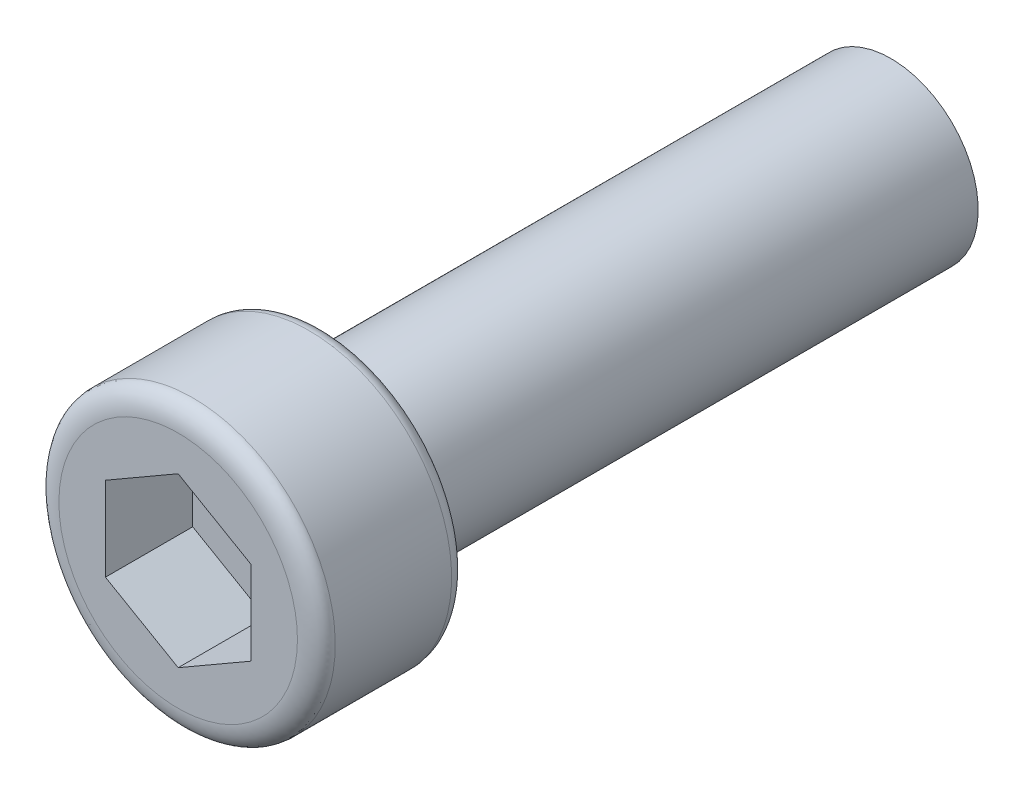
SolidWorks part; units mm, degrees
ref_plane "前视基准面" through (0, 0, 0) normal (0, 0, 1) x (1, 0, 0)
ref_plane "上视基准面" through (0, 0, 0) normal (0, 1, 0) x (1, 0, 0)
ref_plane "右视基准面" through (0, 0, 0) normal (1, 0, 0) x (0, 0, -1)
sketch "草图2" plane through (0, 0, 0) normal (1, 0, 0) x (0, 0, -1)
  line L0 (-12.5, 0) -> (-12.5, 4.9)
  line L1 (-12.5, 4.9) -> (-7.5, 4.9)
  line L2 (-7.5, 4.9) -> (-7.5, 3)
  line L3 (-7.5, 3) -> (12.5, 3)
  line L4 (12.5, 3) -> (12.5, 0)
  line L5 (12.5, 0) -> (-12.5, 0)
  dimension "D1" = 3
  dimension "D2" = 4.9
  dimension "D3" = 5
  dimension "D4" = 20
revolve "旋转1" add sketch "草图2" angle 360 about L5
fillet "圆角1" radius 0.5 1 edges at (-4.9, 0, 7.5)
fillet "圆角2" radius 0.8 1 edges at (-4.9, 0, 12.5) second distance 0.5 first distance on face at (-4.9, 0, 12.5)
chamfer "倒角1" distance 0.5 angle 60 1 edges at (-3, 0, -12.5) first distance on face at (-3, 0, 7.5)
sketch "草图3" plane through (0, 0, 12.5) normal (0, 0, 1) x (1, 0, 0)
  line L1 (0, 2.8868) -> (-2.5, 1.4434)
  line L2 (-2.5, 1.4434) -> (-2.5, -1.4434)
  line L3 (-2.5, -1.4434) -> (0, -2.8868)
  line L4 (0, -2.8868) -> (2.5, -1.4434)
  line L5 (2.5, -1.4434) -> (2.5, 1.4434)
  line L6 (2.5, 1.4434) -> (0, 2.8868)
  circle A0 centre (0, 0) radius 2.5 construction
  dimension "D1" = 5
extrude "切除-拉伸1" cut sketch "草图3" against normal blind 3
